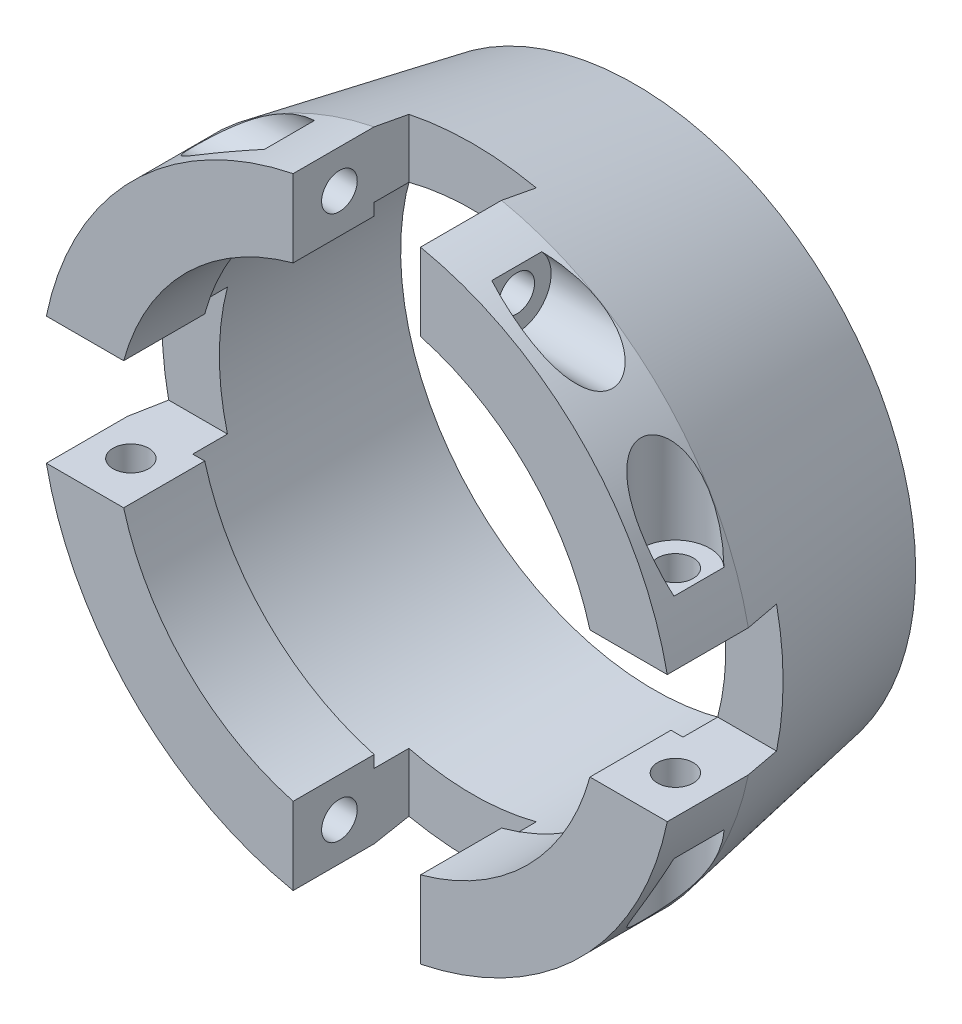
SolidWorks part; units mm, degrees
ref_plane "Front Plane" through (0, 0, 0) normal (1, 0, 0) x (0, 1, 0)
ref_plane "Top Plane" through (0, 0, 0) normal (0, 0, 1) x (0, 1, 0)
ref_plane "Right Plane" through (0, 0, 0) normal (0, 1, 0) x (-1, 0, 0)
sketch "Sketch1" plane through (0, 0, 0) normal (1, 0, 0) x (0, 1, 0)
  line L0 (0, 0) -> (27.7812, 0) construction
  line L1 (0, 0) -> (0, 33.02) construction
  line L2 (27.7812, 0) -> (27.7812, 24.13)
  line L3 (27.7812, 24.13) -> (26.5113, 24.13)
  line L4 (26.5113, 24.13) -> (26.5113, 33.02)
  line L8 (0, 33.02) -> (26.5113, 33.02) construction
  line L11 (27.7812, 0) -> (30.3213, 0)
  line L13 (34.7662, 33.02) -> (26.5113, 33.02)
  line L15 (34.7662, 33.02) -> (34.7662, 24.13)
  line L16 (34.7662, 24.13) -> (30.3213, 0)
  line L17 (27.7812, 24.13) -> (34.7662, 24.13) construction
  point P2 (35.4012, 24.13)
  point P7 (33.105, 0)
  dimension "D1" = 27.7812
  dimension "D2" = 24.13
  dimension "D3" = 8.89
  dimension "D4" = 1.27
  dimension "D5" = 8.255
  dimension "D6" = 2.54
revolve "base_ring" add sketch "Sketch1" angle 360 about L1
sketch "Sketch5" plane through (0, 0, 33.02) normal (0, 0, 1) x (1, 0, 0)
  line L0 (0, 0) -> (0, 25.5745) construction
  line L1 (-6.985, 38.2745) -> (6.985, 38.2745)
  line L2 (-6.985, 38.2745) -> (-6.985, 25.5745)
  line L3 (-6.985, 25.5745) -> (6.985, 25.5745)
  line L4 (6.985, 38.2745) -> (6.985, 25.5745)
  circle A0 centre (0, 0) radius 26.5113 construction
  dimension "D1" = 13.97
  dimension "D2" = 12.7
extrude "pulley_recess" cut sketch "Sketch5" against normal blind 12.7 and the other way through all
ref_plane "Plane1" through (34.7662, 0, 0) normal (1, 0, 0) x (0, 0, -1)
sketch "Sketch7" plane through (34.7662, 0, 0) normal (1, 0, 0) x (0, 0, -1)
  line L6 (-27.94, 29.8663) -> (-27.94, 34.0573) construction
  line L7 (-24.13, 34.0573) -> (-33.02, 34.0573) construction
  line L9 (-24.13, 34.0573) -> (-24.13, -34.7662) construction
  point P0 (-27.94, 29.8663)
  dimension "D1" = 3.81
  dimension "D2" = 4.191
hole_wizard "pulley_bolt_hole" positions "Sketch7" profile "Sketch8" counterbore size "#5" standard "ANSI Inch"
sketch "Sketch8" plane through (34.7662, 29.8663, 27.94) normal (0, 1, 0) x (0, 0, -1)
  line L0 (0, 0) -> (0, 39.2752)
  line L1 (0, 39.2752) -> (1.9558, 38.1)
  line L2 (1.9558, 38.1) -> (1.9558, 22.3012)
  line L3 (1.9558, 22.3012) -> (3.7706, 22.3012)
  line L4 (3.7706, 22.3012) -> (3.7706, 0)
  line L5 (3.7706, 0) -> (0, 0)
  line L10 (0, 39.2752) -> (-1.9558, 38.1) construction
  line L11 (0, -6.35) -> (0, 107.95) construction
  dimension "Hole Dia." = 3.9116
  dimension "Hole Depth" = 38.1
  dimension "C'Bore Dia." = 7.5413
  dimension "C'Bore Depth" = 22.3012
  dimension "Drill Angle" = 118
mirror "bolthole_mirror" about plane through (0, 0, 0) normal (1, 0, 0) of "pulley_bolt_hole"
pattern_circular "CirPattern1" count 4 over 360 about axis through (0, 0, 0) along (0, 0, -1) of "pulley_recess", "pulley_bolt_hole", "bolthole_mirror"
chamfer "Chamfer1" distance 2.54 angle 45 1 edges at (-30.3213, 0, 0) first distance on face at (-30.3213, 0, 0)
